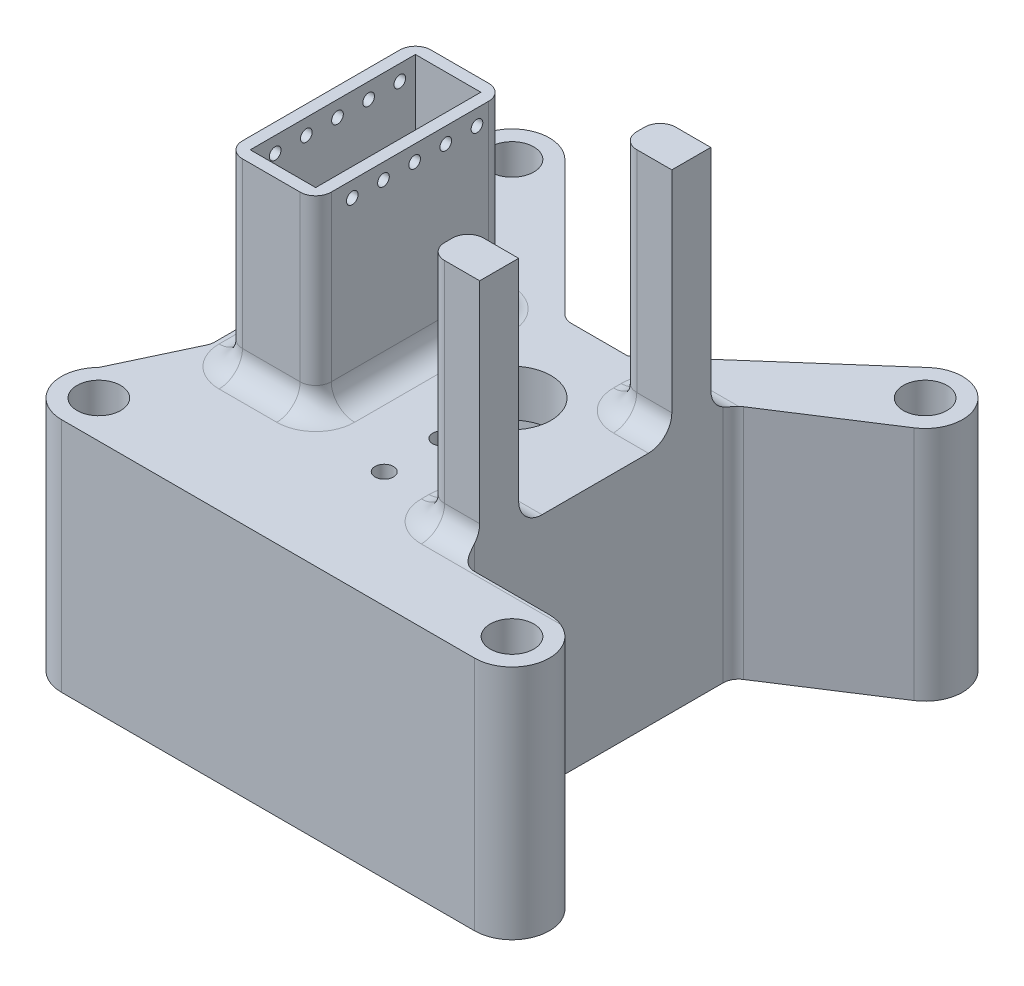
SolidWorks part; units mm, degrees
ref_plane "Front Plane" through (0, 0, 0) normal (0, 0, 1) x (1, 0, 0)
ref_plane "Top Plane" through (0, 0, 0) normal (0, 1, 0) x (1, 0, 0)
ref_plane "Right Plane" through (0, 0, 0) normal (1, 0, 0) x (0, 0, -1)
sketch "Sketch3" plane through (0, 0, 0) normal (0, 1, 0) x (1, 0, 0)
  line L0 (-33.676, -39.772) -> (33.676, -39.772)
  line L1 (-33.676, -33.676) -> (33.676, -33.676) construction
  line L2 (-33.676, -33.676) -> (-33.676, 33.676) construction
  line L3 (-33.676, 33.676) -> (33.676, 33.676) construction
  line L4 (33.676, -33.676) -> (33.676, 33.676) construction
  line L5 (-33.676, -33.676) -> (33.676, 33.676) construction
  line L6 (-33.676, 33.676) -> (33.676, -33.676) construction
  line L7 (10.033, -30.099) -> (-10.033, -30.099)
  line L8 (10.033, -30.099) -> (10.033, 10.033)
  line L9 (10.033, 10.033) -> (3.556, 10.033)
  line L10 (-10.033, -30.099) -> (-10.033, 10.033)
  line L11 (10.033, -30.099) -> (-10.033, 10.033) construction
  line L12 (10.033, 10.033) -> (-10.033, -30.099) construction
  line L13 (33.676, -27.58) -> (18.923, -27.58)
  line L14 (-3.556, 15.367) -> (3.556, 15.367) construction
  line L15 (-3.556, 15.367) -> (-3.556, 10.033)
  line L16 (0, 10.033) -> (3.556, 10.033) construction
  line L17 (3.556, 15.367) -> (3.556, 10.033)
  line L18 (-3.556, 15.367) -> (3.556, 10.033) construction
  line L19 (-3.556, 10.033) -> (3.556, 15.367) construction
  line L20 (-25.781, 10.033) -> (-15.113, 10.033) construction
  line L21 (-25.781, 10.033) -> (-25.781, -16.891) construction
  line L22 (-25.781, -16.891) -> (-15.113, -16.891) construction
  line L23 (-15.113, 10.033) -> (-15.113, -16.891) construction
  line L24 (-25.781, 10.033) -> (-15.113, -16.891) construction
  line L25 (-25.781, -16.891) -> (-15.113, 10.033) construction
  line L26 (18.923, -27.58) -> (18.923, 16.87)
  line L27 (36.9874, 28.5578) -> (18.923, 16.87)
  line L28 (29.6563, 38.259) -> (3.556, 15.367)
  line L31 (0, 10.033) -> (-3.556, 10.033) construction
  line L32 (-29.3669, 37.9879) -> (-6.731, 15.367)
  line L33 (-6.731, 15.367) -> (-3.556, 15.367)
  line L34 (-3.556, 10.033) -> (-10.033, 10.033)
  line L35 (-3.556, 10.033) -> (0, 10.033) construction
  line L36 (3.556, 10.033) -> (0, 10.033) construction
  line L37 (-32.131, -16.891) -> (-32.131, 10.033)
  line L38 (34.003, -24.1637) -> (18.923, -24.1637) construction
  line L39 (34.003, -24.1637) -> (34.003, 13.4537) construction
  line L40 (34.003, 13.4537) -> (18.923, 13.4537) construction
  line L41 (18.923, -24.1637) -> (18.923, 13.4537) construction
  line L42 (34.003, -24.1637) -> (18.923, 13.4537) construction
  line L43 (34.003, 13.4537) -> (18.923, -24.1637) construction
  line L44 (-32.131, 10.033) -> (-39.4519, 31.7268)
  line L45 (-32.131, -16.891) -> (-37.9865, -29.3654)
  circle A0 centre (-33.676, 33.676) radius 3.556
  circle A1 centre (33.676, 33.676) radius 3.556
  circle A2 centre (33.676, -33.676) radius 3.556
  circle A3 centre (-33.676, -33.676) radius 3.556
  circle A4 centre (0, 0) radius 6.35 construction
  circle A5 centre (0, 0) radius 10.033 construction
  circle A6 centre (0, 0) radius 63.373 construction
  arc A7 (33.676, -39.772) -> (33.676, -27.58) centre (33.676, -33.676) ccw
  arc A8 (-39.772, -33.676) -> (-33.676, -39.772) centre (-33.676, -33.676) ccw
  arc A9 (-29.3669, 37.9879) -> (-39.772, 33.676) centre (-33.676, 33.676) ccw
  arc A10 (36.9874, 28.5578) -> (29.6563, 38.259) centre (33.676, 33.676) ccw
  arc A11 (27.58, 33.676) -> (29.3654, 29.3654) centre (33.676, 33.676) ccw construction
  arc A12 (29.6563, 38.259) -> (27.58, 33.676) centre (33.676, 33.676) ccw construction
  arc A13 (29.3654, 29.3654) -> (33.676, 27.58) centre (33.676, 33.676) ccw construction
  arc A14 (33.676, 27.58) -> (36.9874, 28.5578) centre (33.676, 33.676) ccw construction
  arc A15 (-27.58, 33.676) -> (-29.3669, 37.9879) centre (-33.676, 33.676) ccw construction
  arc A16 (-29.3654, 29.3654) -> (-27.58, 33.676) centre (-33.676, 33.676) ccw construction
  arc A17 (-33.676, 27.58) -> (-29.3654, 29.3654) centre (-33.676, 33.676) ccw construction
  arc A18 (-39.772, 33.676) -> (-39.4519, 31.7268) centre (-33.676, 33.676) ccw
  arc A19 (-37.9865, -29.3654) -> (-39.772, -33.676) centre (-33.676, -33.676) ccw
  arc A20 (-29.3654, -29.3654) -> (-33.676, -27.58) centre (-33.676, -33.676) ccw construction
  arc A21 (-27.58, -33.676) -> (-29.3654, -29.3654) centre (-33.676, -33.676) ccw construction
  arc A22 (-33.676, -39.772) -> (-27.58, -33.676) centre (-33.676, -33.676) ccw construction
  arc A23 (33.676, -27.58) -> (29.3654, -29.3654) centre (33.676, -33.676) ccw construction
  arc A24 (29.3654, -29.3654) -> (27.58, -33.676) centre (33.676, -33.676) ccw construction
  arc A25 (27.58, -33.676) -> (33.676, -39.772) centre (33.676, -33.676) ccw construction
  arc A26 (-39.4519, 31.7268) -> (-33.676, 27.58) centre (-33.676, 33.676) ccw construction
  arc A27 (-33.676, -27.58) -> (-37.9865, -29.3654) centre (-33.676, -33.676) ccw construction
  point P0 (0, 0)
  point P10 (0, -10.033)
  point P25 (0, 12.7)
  point P30 (3.556, 12.7)
  point P32 (-20.447, -3.429)
  point P53 (18.923, -5.355)
  point P55 (26.463, -5.355)
  point P64 (-32.131, -3.429)
  dimension "D2" = 7.112
  dimension "D5" = 12.7
  dimension "D6" = 126.746
  dimension "D1" = 95.25
  dimension "D3" = 40.132
  dimension "D4" = 20.066
  dimension "D7" = 2.54
  dimension "D8" = 5.334
  dimension "D9" = 7.112
  dimension "D10" = 10.668
  dimension "D11" = 26.924
  dimension "D12" = 5.08
  dimension "D13" = 8.89
  dimension "D14" = 171.65
  dimension "D15" = 352.506
  dimension "D16" = 44.45
  dimension "D17" = 37.6174
  dimension "D18" = 3.175
  dimension "D19" = 30.16
  dimension "D21" = 6.35
  dimension "D20" = 67.3519
extrude "Boss-Extrude1" add sketch "Sketch3" along normal blind 21.463
sketch "Sketch4" plane through (0, 21.463, 0) normal (0, 1, 0) x (1, 0, 0)
  line L0 (-3.556, 15.367) -> (3.556, 15.367) construction
  line L1 (-3.556, 10.033) -> (3.556, 10.033) construction
  line L2 (3.556, 15.367) -> (-3.556, 15.367)
  line L3 (-3.556, 10.033) -> (3.556, 10.033)
  line L16 (-10.033, 10.033) -> (-3.556, 10.033)
  line L17 (-3.556, 10.033) -> (-3.556, 15.367)
  line L18 (-3.556, 15.367) -> (-6.731, 15.367)
  line L19 (-6.731, 15.367) -> (-29.3669, 37.9879)
  line L20 (-39.4519, 31.7268) -> (-32.131, 10.033)
  line L21 (-33.676, -39.772) -> (33.676, -39.772)
  line L22 (33.676, -27.58) -> (18.923, -27.58)
  line L23 (18.923, -27.58) -> (18.923, 16.87)
  line L24 (18.923, 16.87) -> (36.9874, 28.5578)
  line L25 (29.6563, 38.259) -> (3.556, 15.367)
  line L27 (3.556, 15.367) -> (3.556, 10.033)
  line L28 (3.556, 10.033) -> (10.033, 10.033)
  line L29 (10.033, 10.033) -> (10.033, -30.099)
  line L30 (10.033, -30.099) -> (-10.033, -30.099)
  line L31 (-10.033, -30.099) -> (-10.033, 10.033)
  line L32 (-10.033, 10.033) -> (-3.556, 10.033)
  line L33 (-3.556, 10.033) -> (-3.556, 15.367) construction
  line L34 (-3.556, 15.367) -> (-6.731, 15.367)
  line L35 (-6.731, 15.367) -> (-29.3669, 37.9879)
  line L37 (-33.676, -39.772) -> (33.676, -39.772)
  line L38 (33.676, -27.58) -> (18.923, -27.58)
  line L39 (18.923, -27.58) -> (18.923, 16.87)
  line L40 (18.923, 16.87) -> (36.9874, 28.5578)
  line L41 (29.6563, 38.259) -> (3.556, 15.367)
  line L43 (3.556, 15.367) -> (3.556, 10.033) construction
  line L44 (3.556, 10.033) -> (10.033, 10.033)
  line L45 (10.033, 10.033) -> (10.033, -30.099)
  line L46 (10.033, -30.099) -> (-10.033, -30.099)
  line L47 (-10.033, -30.099) -> (-10.033, 10.033)
  line L52 (-39.4519, 31.7268) -> (-32.131, 10.033)
  line L53 (-32.131, 10.033) -> (-32.131, -16.891)
  line L54 (-32.131, 10.033) -> (-32.131, -16.891)
  line L55 (-32.131, -16.891) -> (-37.9865, -29.3654)
  line L56 (-32.131, -16.891) -> (-37.9865, -29.3654)
  circle A3 centre (33.676, -33.676) radius 3.556 construction
  arc A4 (-29.3669, 37.9879) -> (-39.4519, 31.7268) centre (-33.676, 33.676) ccw
  arc A5 (-37.9865, -29.3654) -> (-33.676, -39.772) centre (-33.676, -33.676) ccw
  arc A6 (33.676, -39.772) -> (33.676, -27.58) centre (33.676, -33.676) ccw
  arc A7 (36.9874, 28.5578) -> (29.6563, 38.259) centre (33.676, 33.676) ccw
  arc A8 (-29.3669, 37.9879) -> (-39.4519, 31.7268) centre (-33.676, 33.676) ccw
  arc A9 (-37.9865, -29.3654) -> (-33.676, -39.772) centre (-33.676, -33.676) ccw
  arc A10 (33.676, -39.772) -> (33.676, -27.58) centre (33.676, -33.676) ccw
  arc A11 (36.9874, 28.5578) -> (29.6563, 38.259) centre (33.676, 33.676) ccw
  circle A12 centre (33.676, -33.676) radius 3.556
  circle A13 centre (33.676, 33.676) radius 3.556 construction
  circle A14 centre (33.676, 33.676) radius 3.556
  circle A15 centre (-33.676, 33.676) radius 3.556 construction
  circle A16 centre (-33.676, 33.676) radius 3.556
  circle A17 centre (-33.676, -33.676) radius 3.556 construction
  circle A18 centre (-33.676, -33.676) radius 3.556
  dimension "D1" = 0
extrude "Boss-Extrude2" add sketch "Sketch4" along normal blind 7.366
sketch "Sketch5" plane through (0, 28.829, 0) normal (0, 1, 0) x (1, 0, 0)
  line L8 (3.556, 15.367) -> (-6.731, 15.367)
  line L9 (-6.731, 15.367) -> (-29.3669, 37.9879)
  line L10 (-39.4519, 31.7268) -> (-32.131, 10.033)
  line L11 (-33.676, -39.772) -> (33.676, -39.772)
  line L12 (33.676, -27.58) -> (18.923, -27.58)
  line L13 (18.923, -27.58) -> (18.923, 16.87)
  line L14 (18.923, 16.87) -> (36.9874, 28.5578)
  line L15 (29.6563, 38.259) -> (3.556, 15.367)
  line L16 (3.556, 15.367) -> (-6.731, 15.367)
  line L17 (-6.731, 15.367) -> (-29.3669, 37.9879)
  line L19 (-33.676, -39.772) -> (33.676, -39.772)
  line L20 (33.676, -27.58) -> (18.923, -27.58)
  line L21 (18.923, -27.58) -> (18.923, 16.87)
  line L22 (18.923, 16.87) -> (36.9874, 28.5578)
  line L23 (29.6563, 38.259) -> (3.556, 15.367)
  line L26 (-39.4519, 31.7268) -> (-32.131, 10.033)
  line L27 (-32.131, 10.033) -> (-32.131, -16.891)
  line L28 (-32.131, 10.033) -> (-32.131, -16.891)
  line L29 (-32.131, -16.891) -> (-37.9865, -29.3654)
  line L30 (-32.131, -16.891) -> (-37.9865, -29.3654)
  circle A0 centre (0, 0) radius 6.35 construction
  circle A1 centre (33.676, 33.676) radius 3.556
  circle A2 centre (33.676, 33.676) radius 3.556
  circle A3 centre (-33.676, 33.676) radius 3.556
  circle A4 centre (-33.676, 33.676) radius 3.556
  circle A5 centre (-33.676, -33.676) radius 3.556
  circle A6 centre (-33.676, -33.676) radius 3.556
  circle A7 centre (33.676, -33.676) radius 3.556
  circle A8 centre (33.676, -33.676) radius 3.556
  circle A9 centre (0, 0) radius 6.35
  arc A12 (-29.3669, 37.9879) -> (-39.4519, 31.7268) centre (-33.676, 33.676) ccw
  arc A13 (-37.9865, -29.3654) -> (-33.676, -39.772) centre (-33.676, -33.676) ccw
  arc A14 (33.676, -39.772) -> (33.676, -27.58) centre (33.676, -33.676) ccw
  arc A15 (36.9874, 28.5578) -> (29.6563, 38.259) centre (33.676, 33.676) ccw
  arc A16 (-29.3669, 37.9879) -> (-39.4519, 31.7268) centre (-33.676, 33.676) ccw
  arc A17 (-37.9865, -29.3654) -> (-33.676, -39.772) centre (-33.676, -33.676) ccw
  arc A18 (33.676, -39.772) -> (33.676, -27.58) centre (33.676, -33.676) ccw
  arc A19 (36.9874, 28.5578) -> (29.6563, 38.259) centre (33.676, 33.676) ccw
  dimension "D1" = 0
  dimension "D2" = 0
  dimension "D3" = 0
  dimension "D4" = 0
  dimension "D5" = 0
extrude "Boss-Extrude3" add sketch "Sketch5" along normal blind 7.62
sketch "Sketch6" plane through (0, 36.449, 0) normal (0, 1, 0) x (1, 0, 0)
  line L0 (-25.781, 10.033) -> (-25.781, -16.891) construction
  line L1 (-25.781, -16.891) -> (-15.113, -16.891) construction
  line L2 (-15.113, 10.033) -> (-15.113, -16.891) construction
  line L3 (-25.781, 10.033) -> (-15.113, 10.033) construction
  line L4 (-25.781, 10.033) -> (-25.781, -16.891) construction
  line L5 (-25.781, -16.891) -> (-15.113, -16.891) construction
  line L6 (-15.113, 10.033) -> (-15.113, -16.891) construction
  line L7 (-25.781, 10.033) -> (-15.113, 10.033) construction
  line L9 (-13.208, 11.938) -> (-27.686, 11.938)
  line L10 (-13.208, 11.938) -> (-13.208, -18.796)
  line L11 (-13.208, -18.796) -> (-27.686, -18.796)
  line L12 (-27.686, 11.938) -> (-27.686, -18.796)
  line L13 (-13.208, 11.938) -> (-27.686, -18.796) construction
  line L14 (-13.208, -18.796) -> (-27.686, 11.938) construction
  point P4 (-20.447, -3.429)
  point P11 (-20.447, -16.891)
  dimension "D1" = 1.905
  dimension "D2" = 1.905
extrude "Boss-Extrude4" add sketch "Sketch6" along normal blind 30.59
sketch "Sketch7" plane through (0, 67.039, 0) normal (0, 1, 0) x (1, 0, 0)
  line L0 (-25.781, 10.033) -> (-25.781, -16.891) construction
  line L1 (-25.781, -16.891) -> (-15.113, -16.891) construction
  line L2 (-15.113, 10.033) -> (-15.113, -16.891) construction
  line L3 (-25.781, 10.033) -> (-15.113, 10.033) construction
  line L4 (-25.781, 10.033) -> (-25.781, -16.891)
  line L5 (-25.781, -16.891) -> (-15.113, -16.891)
  line L6 (-15.113, 10.033) -> (-15.113, -16.891)
  line L7 (-25.781, 10.033) -> (-15.113, 10.033)
extrude "Cut-Extrude1" cut sketch "Sketch7" against normal blind 50.8
sketch "Sketch8" plane through (-27.686, 0, 0) normal (-1, 0, 0) x (0, 0, 1)
  line L0 (16.891, 16.239) -> (16.891, 67.039) construction
  line L1 (-10.033, 16.239) -> (-10.033, 67.039) construction
  line L2 (16.891, 16.239) -> (16.891, 67.039) construction
  line L3 (-10.033, 16.239) -> (-10.033, 67.039) construction
  line L4 (-7.493, 64.499) -> (-2.413, 64.499) construction
  circle A0 centre (-7.493, 64.499) radius 0.9525
  circle A1 centre (-2.413, 64.499) radius 0.9525
  circle A2 centre (2.667, 64.499) radius 0.9525
  circle A3 centre (7.747, 64.499) radius 0.9525
  circle A4 centre (12.827, 64.499) radius 0.9525
  dimension "D1" = 1.905
  dimension "D5" = 5.08
  dimension "D2" = 2.54
  dimension "D3" = 2.54
  dimension "D4" = 5
extrude "Cut-Extrude2" cut sketch "Sketch8" against normal through all
sketch "Sketch10" plane through (0, 36.449, 0) normal (0, 1, 0) x (1, 0, 0)
  line L0 (18.923, -27.58) -> (18.923, 16.87) construction
  line L1 (10.668, -24.19) -> (18.923, -24.19)
  line L2 (10.668, -24.19) -> (10.668, -17.84)
  line L3 (10.668, 13.48) -> (18.923, 13.48)
  line L4 (18.923, -24.19) -> (18.923, -17.84)
  line L5 (10.668, -24.19) -> (18.923, 13.48) construction
  line L6 (10.668, 13.48) -> (18.923, -24.19) construction
  line L7 (18.923, -27.58) -> (18.923, 16.87) construction
  line L8 (18.923, -17.84) -> (18.923, 7.13) construction
  line L9 (18.923, -17.84) -> (10.668, -17.84)
  line L10 (18.923, -17.84) -> (18.923, 7.13) construction
  line L11 (18.923, 7.13) -> (10.668, 7.13)
  line L12 (10.668, -17.84) -> (10.668, 7.13) construction
  line L13 (18.923, -17.84) -> (10.668, 7.13) construction
  line L14 (18.923, 7.13) -> (10.668, -17.84) construction
  line L15 (18.923, 7.13) -> (18.923, 13.48)
  line L16 (10.668, -17.84) -> (10.668, 7.13) construction
  line L17 (10.668, 7.13) -> (10.668, 13.48)
  point P0 (14.7955, -5.355)
  point P7 (18.923, -5.355)
  point P9 (14.7955, -5.355)
  dimension "D1" = 37.67
  dimension "D2" = 8.255
  dimension "D3" = 6.35
extrude "Boss-Extrude5" add sketch "Sketch10" along normal blind 38.1
sketch "Sketch9" plane through (18.923, 0, 0) normal (1, 0, 0) x (0, 0, -1)
  line L0 (-27.58, 0) -> (16.87, 0) construction
  line L1 (-21.205, 71.3) -> (10.495, 71.3) construction
  line L2 (-21.205, 71.3) -> (-21.205, 5) construction
  line L3 (-21.205, 5) -> (10.495, 5) construction
  line L4 (10.495, 71.3) -> (10.495, 5) construction
  line L5 (-21.205, 71.3) -> (10.495, 5) construction
  line L6 (-21.205, 5) -> (10.495, 71.3) construction
  circle A0 centre (-21.205, 71.3) radius 1.524
  circle A1 centre (10.495, 71.3) radius 1.524
  circle A2 centre (10.495, 5) radius 1.524
  circle A3 centre (-21.205, 5) radius 1.524
  circle A4 centre (-5.355, 38.15) radius 38.2683
  point P0 (-5.355, 38.15)
  dimension "D4" = 3.048
  dimension "D1" = 31.7
  dimension "D2" = 66.3
  dimension "D3" = 5
extrude "Cut-Extrude3" cut sketch "Sketch9" against normal blind 5.75 rebuild error yes
sketch "Sketch13" plane through (0, 36.449, 0) normal (0, 1, 0) x (1, 0, 0)
  line L0 (0, -11.43) -> (0, -20.828) construction
  circle A0 centre (0, -11.43) radius 1.5
  circle A1 centre (0, -20.828) radius 1.5
  dimension "D2" = 3
  dimension "D1" = 9.398
  dimension "D3" = 11.43
extrude "Cut-Extrude4" cut sketch "Sketch13" against normal blind 4
fillet "Fillet1" radius 2.54 13 edges at (10.668, 55.499, 17.84) (10.668, 55.499, 24.19) (10.668, 55.499, -7.13) (10.668, 55.499, -13.48) (-27.686, 51.744, -11.938) (-13.208, 51.744, -11.938) (-13.208, 51.744, 18.796) (-27.686, 51.744, 18.796) (-32.131, 18.2245, 16.891) (-32.131, 18.2245, -10.033) (-6.731, 18.2245, -15.367) (18.923, 18.2245, -16.87) (18.923, 18.2245, 27.58)
fillet "Fillet2" radius 3.81 18 edges at (-13.9519, 36.449, -11.1941) (-13.208, 36.449, 3.429) (-13.9519, 36.449, 18.0521) (-20.447, 36.449, 18.796) (-26.9421, 36.449, 18.0521) (-27.686, 36.449, 3.429) (-26.9421, 36.449, -11.1941) (16.0655, 36.449, 24.19) (11.4119, 36.449, 23.446) (10.668, 36.449, 21.015) (11.4119, 36.449, 18.5839) (16.0655, 36.449, -7.13) (11.4119, 36.449, -7.874) (10.668, 36.449, -10.305) (11.4119, 36.449, -12.7361) (-20.447, 36.449, -11.938) (16.0655, 36.449, 17.84) (16.0655, 36.449, -13.48)
sketch "Sketch14" plane through (0, 0, 0) normal (0, -1, 0) x (1, 0, 0)
  line L17 (-3.556, -10.033) -> (-10.033, -10.033)
  line L18 (-10.033, -10.033) -> (-10.033, 30.099)
  line L19 (-10.033, 30.099) -> (10.033, 30.099)
  line L20 (10.033, 30.099) -> (10.033, -10.033)
  line L21 (10.033, -10.033) -> (3.556, -10.033)
  line L22 (3.556, -10.033) -> (3.556, -15.367)
  line L23 (3.556, -15.367) -> (29.6563, -38.259)
  line L24 (36.9874, -28.5578) -> (20.0832, -17.6207)
  line L25 (18.923, -15.4881) -> (18.923, 25.04)
  line L26 (21.463, 27.58) -> (33.676, 27.58)
  line L27 (33.676, 39.772) -> (-33.676, 39.772)
  line L28 (-37.9865, 29.3654) -> (-32.3717, 17.4038)
  line L29 (-32.131, 16.3245) -> (-32.131, -9.616)
  line L30 (-32.2643, -10.4281) -> (-39.4519, -31.7268)
  line L31 (-29.3669, -37.9879) -> (-7.4748, -16.1104)
  line L32 (-5.6794, -15.367) -> (-3.556, -15.367)
  line L33 (-3.556, -15.367) -> (-3.556, -10.033)
  line L34 (-3.556, -10.033) -> (-10.033, -10.033)
  line L35 (-10.033, -10.033) -> (-10.033, 30.099)
  line L36 (-10.033, 30.099) -> (10.033, 30.099)
  line L37 (10.033, 30.099) -> (10.033, -10.033)
  line L38 (10.033, -10.033) -> (3.556, -10.033)
  line L39 (3.556, -10.033) -> (3.556, -15.367)
  line L40 (3.556, -15.367) -> (29.6563, -38.259)
  line L41 (36.9874, -28.5578) -> (20.0832, -17.6207)
  line L42 (18.923, -15.4881) -> (18.923, 25.04)
  line L43 (21.463, 27.58) -> (33.676, 27.58)
  line L44 (33.676, 39.772) -> (-33.676, 39.772)
  line L45 (-37.9865, 29.3654) -> (-32.3717, 17.4038)
  line L46 (-32.131, 16.3245) -> (-32.131, -9.616)
  line L47 (-32.2643, -10.4281) -> (-39.4519, -31.7268)
  line L48 (-29.3669, -37.9879) -> (-7.4748, -16.1104)
  line L49 (-5.6794, -15.367) -> (-3.556, -15.367)
  line L50 (-3.556, -15.367) -> (-3.556, -10.033)
  circle A0 centre (-33.676, -33.676) radius 3.556 construction
  circle A1 centre (-33.676, -33.676) radius 3.556
  circle A2 centre (-33.676, 33.676) radius 3.556 construction
  circle A3 centre (-33.676, 33.676) radius 3.556
  circle A4 centre (33.676, 33.676) radius 3.556 construction
  circle A5 centre (33.676, 33.676) radius 3.556
  circle A6 centre (33.676, -33.676) radius 3.556 construction
  circle A7 centre (33.676, -33.676) radius 3.556
  arc A9 (29.6563, -38.259) -> (36.9874, -28.5578) centre (33.676, -33.676) ccw
  arc A10 (18.923, -15.4881) -> (20.0832, -17.6207) centre (21.463, -15.4881) ccw
  arc A11 (21.463, 27.58) -> (18.923, 25.04) centre (21.463, 25.04) ccw
  arc A12 (33.676, 27.58) -> (33.676, 39.772) centre (33.676, 33.676) ccw
  arc A13 (-33.676, 39.772) -> (-37.9865, 29.3654) centre (-33.676, 33.676) ccw
  arc A14 (-32.131, 16.3245) -> (-32.3717, 17.4038) centre (-34.671, 16.3245) ccw
  arc A15 (-32.2643, -10.4281) -> (-32.131, -9.616) centre (-34.671, -9.616) ccw
  arc A16 (-39.4519, -31.7268) -> (-29.3669, -37.9879) centre (-33.676, -33.676) ccw
  arc A17 (-5.6794, -15.367) -> (-7.4748, -16.1104) centre (-5.6794, -17.907) ccw
  arc A18 (29.6563, -38.259) -> (36.9874, -28.5578) centre (33.676, -33.676) ccw
  arc A19 (18.923, -15.4881) -> (20.0832, -17.6207) centre (21.463, -15.4881) ccw
  arc A20 (21.463, 27.58) -> (18.923, 25.04) centre (21.463, 25.04) ccw
  arc A21 (33.676, 27.58) -> (33.676, 39.772) centre (33.676, 33.676) ccw
  arc A22 (-33.676, 39.772) -> (-37.9865, 29.3654) centre (-33.676, 33.676) ccw
  arc A23 (-32.131, 16.3245) -> (-32.3717, 17.4038) centre (-34.671, 16.3245) ccw
  arc A24 (-32.2643, -10.4281) -> (-32.131, -9.616) centre (-34.671, -9.616) ccw
  arc A25 (-39.4519, -31.7268) -> (-29.3669, -37.9879) centre (-33.676, -33.676) ccw
  arc A26 (-5.6794, -15.367) -> (-7.4748, -16.1104) centre (-5.6794, -17.907) ccw
  dimension "D1" = 0
extrude "Boss-Extrude6" add sketch "Sketch14" along normal blind 2.0585
equation "\"AIRFRAME_OD\"= 5.15in"
equation "\"AIRFRAME_ID\"= 4.99in"
equation "\"FLAT_T\"= 0.125in"
equation "\"COUPLER_OD\"= 4.998in"
equation "\"COUPLER_ID\"= 4.85in"
equation "\"NOSE_EXP_L\"= 27in"
equation "\"NOSE_SHOULDER_L\"= 5in"
equation "\"MAIN_L\"= 30in"
equation "\"RECO_COUP_L\"= 10in"
equation "\"RECO_SWITCH_L\"= 2in"
equation "\"RECO_ROD_X\"= 3.5in"
equation "\"DROGUE_L\"= 20in"
equation "\"ATS_FORE_COUP_L\"= 5.5in"
equation "\"ATS_AFT_COUP_L\"= 4.5in"
equation "\"ATS_ROD_X\"= 3.75in"
equation "\"LOWER_L\"= 30in"
equation "\"FIN_ROOT\"= 8in"
equation "\"FIN_X\"= 0.75in"
equation "\"FIN_N\"= 4"
equation "\"MOTOR_OD\"= 3.091in"
equation "\"MOTOR_ID\"= 3.00in"
equation "\"MOTOR_L\"= 14in"
equation "\"CR_AFT_X\"= 0.5in"
equation "\"CR_FORE_X\"= 9.25in"
equation "\"MOTOR_LOWER_X\"= 2in"
equation "\"D1@Sketch3\"=\"ATS_ROD_X\""
equation "\"D6@Sketch3\"=\"AIRFRAME_ID\""
